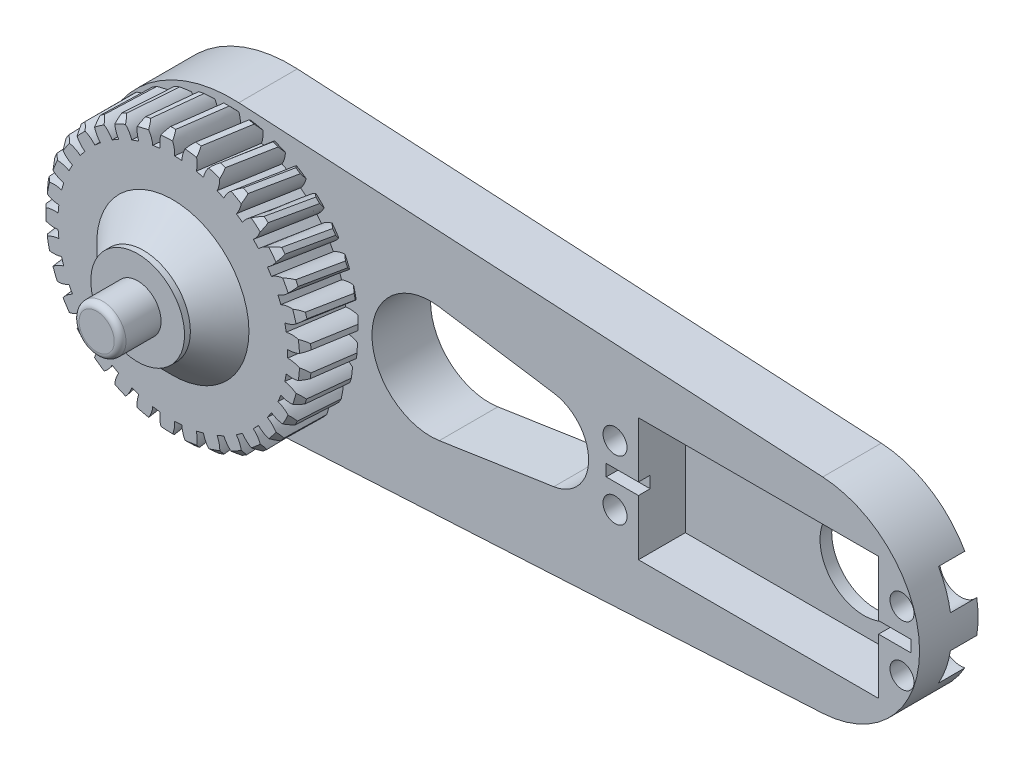
SolidWorks part; units mm, degrees
ref_plane "Front Plane" through (0, 0, 0) normal (1, 0, 0) x (0, 1, 0)
ref_plane "Top Plane" through (0, 0, 0) normal (0, 0, 1) x (0, 1, 0)
ref_plane "Right Plane" through (0, 0, 0) normal (0, 1, 0) x (-1, 0, 0)
sketch "Sketch5" plane through (0, 0, 0) normal (0, 0, 1) x (0, 1, 0)
  circle A0 centre (0, 0) radius 22.65
  dimension "D1" = 45.3
extrude "Boss-Extrude1" add sketch "Sketch5" along normal blind 10
chamfer "Chamfer1" distance 1 angle 45 2 edges at (22.65, 0, 10) (22.65, 0, 0)
sketch "Sketch9" plane through (0, 0, 10) normal (0, 0, 1) x (1, 0, 0)
  circle A0 centre (0, 0) radius 22.65 construction
  circle A1 centre (0, 0) radius 22.65
curve "Helix/Spiral1" pitch 1030.9278 height 20 radius 22.65 centre (0, 0, 10) axis (0, 0, -1) start towards (-1, 0, 0)
sketch "Sketch10" plane through (0, 0, 10) normal (0, 0, 1) x (1, 0, 0)
  line L0 (0, 0) -> (31, 0) construction
  line L1 (19.6061, 0.64) -> (19.6061, -0.64)
  circle A0 centre (0, 0) radius 22.65 construction
  arc A1 (22.5861, -1.7) -> (22.5861, 1.7) centre (0, 0) ccw
  arc A2 (19.6061, 0.64) -> (22.5861, 1.7) centre (19.7705, 4.8968) ccw
  arc A3 (19.6061, -0.64) -> (22.5861, -1.7) centre (19.7705, -4.8968) cw
  point P9 (19.6061, 0)
  dimension "D2" = 3.4
  dimension "D4" = 4.26
  dimension "D1" = 1.28
  dimension "D3" = 2.98
sweep "Cut-Sweep1" cut profiles "Sketch10" path "Helix/Spiral1" align with end faces yes
pattern_circular "CirPattern1" count 33 over 360 about axis through (0, 0, 10) along (0, 0, -1) of "Cut-Sweep1" reverse direction yes
sketch "Sketch11" plane through (0, 0, 0) normal (0, 0, 1) x (0, 1, 0)
  circle A0 centre (0, 0) radius 8
  dimension "D1" = 16
extrude "Boss-Extrude2" add sketch "Sketch11" along normal blind 6 from surface starting at face at (0, 0, 10)
sketch "Sketch12" plane through (0, 0, 0) normal (0, 0, 1) x (0, 1, 0)
  circle A0 centre (0, 0) radius 4
  dimension "D1" = 8
extrude "Boss-Extrude3" add sketch "Sketch12" along normal blind 7 from surface starting at face at (8, 0, 16)
fillet "Fillet1" radius 1 1 edges at (4, 0, 23)
chamfer "Chamfer3" distance 5 angle 45 1 edges at (8, 0, 10)
sketch "Sketch13" plane through (0, 0, 0) normal (0, 0, 1) x (0, 1, 0)
  line L0 (0, 0) -> (0, -39.3295) construction
  line L1 (-17.4735, -100.9625) -> (-22.9652, -1.265)
  line L2 (17.4735, -100.9625) -> (22.9652, -1.265)
  line L3 (-9.8869, -35.5) -> (-6.9208, -55.05)
  line L4 (9.8869, -35.5) -> (6.9208, -55.05)
  arc A0 (22.9652, -1.265) -> (-22.9652, -1.265) centre (0, 0) ccw
  arc A1 (-17.4735, -100.9625) -> (17.4735, -100.9625) centre (0, -100) ccw
  arc A2 (-6.9208, -55.05) -> (6.9208, -55.05) centre (0, -54) ccw
  arc A3 (9.8869, -35.5) -> (-9.8869, -35.5) centre (0, -34) ccw
  circle A5 centre (0, -100) radius 5
  dimension "D1" = 46
  dimension "D2" = 35
  dimension "D6" = 10
  dimension "D7" = 7
  dimension "D8" = 10
  dimension "D3" = 100
  dimension "D4" = 34
  dimension "D5" = 20
extrude "Boss-Extrude5" add sketch "Sketch13" against normal blind 10
sketch "Sketch14" plane through (0, 0, 0) normal (0, 0, 1) x (0, 1, 0)
  circle A0 centre (0, -100) radius 7.5
  dimension "D1" = 15
extrude "Cut-Extrude1" cut sketch "Sketch14" along normal blind 7.1 from surface starting at face at (43.8875, 0, -10)
sketch "Sketch16" plane through (0, 0, 0) normal (0, 0, 1) x (0, 1, 0)
  line L0 (0, -100) -> (0, -65.5) construction
  line L1 (0, -100) -> (0, -114.5) construction
  line L3 (-12.5, -62) -> (12.5, -62)
  line L4 (-12.5, -62) -> (-12.5, -69)
  line L5 (-12.5, -69) -> (12.5, -69)
  line L6 (12.5, -62) -> (12.5, -69)
  line L7 (-12.5, -62) -> (12.5, -69) construction
  line L8 (-12.5, -69) -> (12.5, -62) construction
  line L9 (-12.5, -111) -> (12.5, -111)
  line L10 (-12.5, -111) -> (-12.5, -112.2474)
  line L12 (12.5, -111) -> (12.5, -112.2474)
  arc A0 (-12.5, -112.2474) -> (12.5, -112.2474) centre (0, -100) ccw
  dimension "D1" = 34.5
  dimension "D2" = 14.5
  dimension "D3" = 25
  dimension "D4" = 7
  dimension "D5" = 25
sketch "Sketch15" plane through (0, 0, 0) normal (0, 0, 1) x (0, 1, 0)
  line L0 (0, 0) -> (0, -52.2327) construction
  line L1 (0, -100) -> (0, -114.5) construction
  line L2 (0, -114.5) -> (5.1, -114.5) construction
  line L3 (0, -90) -> (8.1325, -90) construction
  line L5 (-10.5, -69.5) -> (10.5, -69.5) construction
  line L6 (-10.5, -69.5) -> (-10.5, -110.5) construction
  line L7 (-10.5, -110.5) -> (10.5, -110.5) construction
  line L8 (10.5, -69.5) -> (10.5, -110.5) construction
  line L9 (-10.5, -69.5) -> (10.5, -110.5) construction
  line L10 (-10.5, -110.5) -> (10.5, -69.5) construction
  circle A0 centre (5.1, -114.5) radius 2.05
  circle A1 centre (-5.1, -114.5) radius 2.05
  circle A2 centre (5.1, -65.5) radius 2.05
  circle A3 centre (-5.1, -65.5) radius 2.05
  point P16 (0, -90)
  point P21 (0, -69.5)
  dimension "D3" = 4.1
  dimension "D1" = 14.5
  dimension "D2" = 5.1
  dimension "D4" = 24.5
  dimension "D5" = 21
  dimension "D6" = 41
  dimension "D7" = 4
extrude "Cut-Extrude2" cut sketch "Sketch15" against normal blind 10
sketch "Sketch17" plane through (0, 0, 0) normal (0, 0, 1) x (0, 1, 0)
  line L1 (-10.5, -69.5) -> (10.5, -69.5)
  line L2 (-10.5, -69.5) -> (-10.5, -110.5)
  line L3 (-10.5, -110.5) -> (10.5, -110.5)
  line L4 (10.5, -69.5) -> (10.5, -110.5)
  line L5 (-10.5, -69.5) -> (10.5, -110.5) construction
  line L6 (-10.5, -110.5) -> (10.5, -69.5) construction
  point P0 (0, -90)
extrude "Cut-Extrude3" cut sketch "Sketch17" against normal blind 8 from surface starting at face at (112.45, -5.1, 0)
sketch "Sketch18" plane through (0, 0, 0) normal (0, 0, 1) x (0, 1, 0)
  line L0 (-10.5, -110.5) -> (10.5, -69.5) construction
  line L1 (1, -116) -> (-1, -116)
  line L2 (1, -116) -> (1, -64)
  line L3 (1, -64) -> (-1, -64)
  line L4 (-1, -116) -> (-1, -64)
  line L5 (1, -116) -> (-1, -64) construction
  line L6 (1, -64) -> (-1, -116) construction
  point P0 (0, -90)
  dimension "D1" = 52
  dimension "D2" = 2
extrude "Cut-Extrude4" cut sketch "Sketch18" against normal blind 2 from surface starting at face at (49.1819, 0, 0)
sketch "Sketch19" plane through (0, 0, 0) normal (0, 0, 1) x (0, 1, 0)
  circle A0 centre (5.1, -65.5) radius 3.6
  circle A1 centre (-5.1, -65.5) radius 3.6
  circle A2 centre (5.1, -114.5) radius 3.6
  circle A3 centre (-5.1, -114.5) radius 3.6
  dimension "D1" = 7.2
  dimension "D2" = 7.2
  dimension "D3" = 7.2
  dimension "D4" = 7.2
extrude "Cut-Extrude5" cut sketch "Sketch19" along normal blind 4.5 from surface starting at face at (112.45, -5.1, -10)
